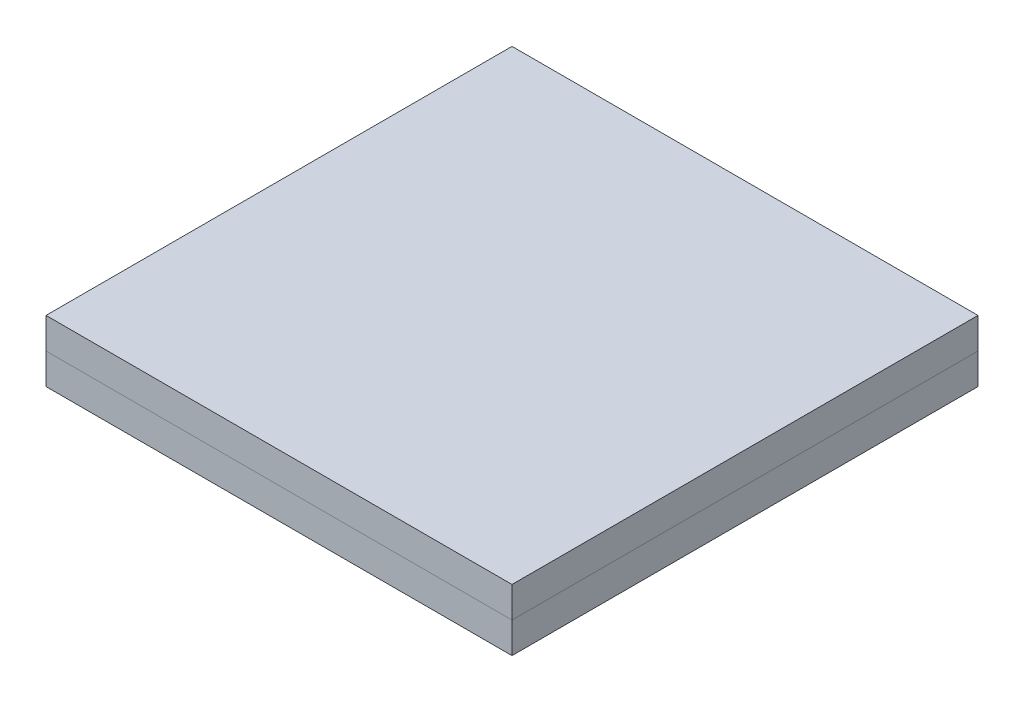
SolidWorks part; units mm, degrees
ref_plane "Front Plane" through (0, 0, 0) normal (0, 0, 1) x (1, 0, 0)
ref_plane "Top Plane" through (0, 0, 0) normal (0, 1, 0) x (1, 0, 0)
ref_plane "Right Plane" through (0, 0, 0) normal (1, 0, 0) x (0, 0, -1)
sketch "Sketch1" plane through (0, 0, 0) normal (0, 1, 0) x (1, 0, 0)
  line L1 (-12, -12) -> (12, -12)
  line L2 (-12, -12) -> (-12, 12)
  line L3 (-12, 12) -> (12, 12)
  line L4 (12, -12) -> (12, 12)
  line L5 (-12, -12) -> (12, 12) construction
  line L6 (-12, 12) -> (12, -12) construction
  point P0 (0, 0)
  dimension "D1" = 24
extrude "Boss-Extrude1" add sketch "Sketch1" along normal blind 3.175
ref_plane "Plane1" through (0, 1.5875, 0) normal (0, 1, 0) x (1, 0, 0)
split "Split1" trim tools "Plane1" bodies to split 101 resulting bodies 102 103
